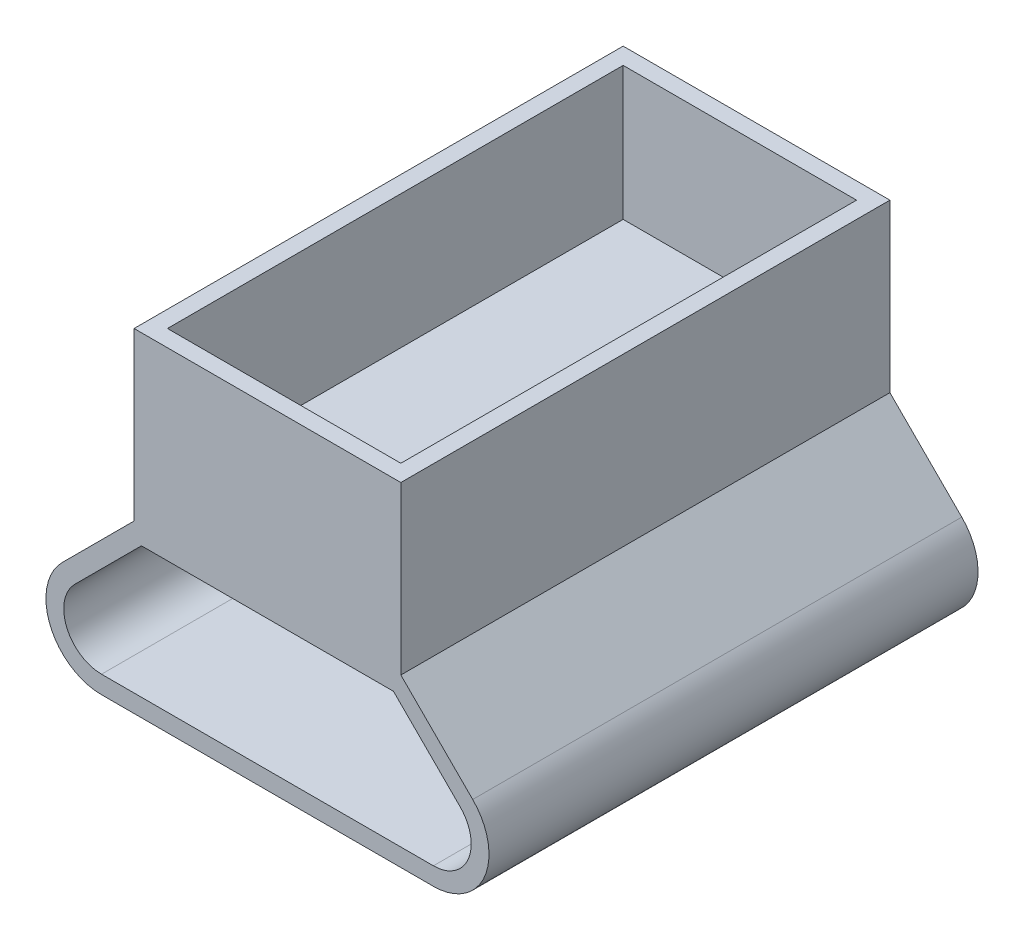
SolidWorks part; units mm, degrees
ref_plane "Front Plane" through (0, 0, 0) normal (0, 0, 1) x (1, 0, 0)
ref_plane "Top Plane" through (0, 0, 0) normal (0, 1, 0) x (1, 0, 0)
ref_plane "Right Plane" through (0, 0, 0) normal (1, 0, 0) x (0, 0, -1)
sketch "Sketch1" plane through (0, 0, 0) normal (0, 0, 1) x (1, 0, 0)
  line L0 (-12, 0) -> (12, 0)
  line L1 (-12, 0) -> (-18.4645, -6.4645)
  line L2 (-14.9289, -15) -> (14.9289, -15)
  line L3 (18.4645, -6.4645) -> (12, 0)
  arc A0 (-18.4645, -6.4645) -> (-14.9289, -15) centre (-14.9289, -10) ccw
  arc A1 (14.9289, -15) -> (18.4645, -6.4645) centre (14.9289, -10) ccw
  point P3 (-2.6993, 0)
  point P4 (0, 0)
  point P6 (0, 0)
  point P8 (-26.4535, -21.1639)
  point P9 (-33.5712, -21.6785)
  point P10 (-15.8198, 0)
  point P11 (-29.6264, -23.1363)
  point P12 (-16.9347, 0)
  point P13 (-16.3344, 0)
  point P14 (-16.4633, 0)
  point P15 (-33.2222, -17.6443)
  point P16 (-24.3682, -13.3682)
  point P17 (-26.5483, -15.5483)
  point P18 (-27.568, -16.568)
  dimension "D4" = 5
  dimension "D1" = 45
  dimension "D2" = 24
  dimension "D3" = 15
extrude "Boss-Extrude1" add sketch "Sketch1" along normal blind 44
sketch "Sketch3" plane through (0, 0, 44) normal (0, 0, 1) x (1, 0, 0)
  line L27 (-14.9289, -13.4) -> (14.9289, -13.4)
  line L28 (17.3331, -7.5958) -> (11.3373, -1.6)
  line L29 (11.3373, -1.6) -> (-11.3373, -1.6)
  line L30 (-11.3373, -1.6) -> (-17.3331, -7.5958)
  line L31 (-14.9289, -13.4) -> (14.9289, -13.4)
  line L32 (17.3331, -7.5958) -> (11.3373, -1.6)
  line L33 (11.3373, -1.6) -> (-11.3373, -1.6)
  line L34 (-11.3373, -1.6) -> (-17.3331, -7.5958)
  arc A6 (14.9289, -13.4) -> (17.3331, -7.5958) centre (14.9289, -10) ccw
  arc A7 (-17.3331, -7.5958) -> (-14.9289, -13.4) centre (-14.9289, -10) ccw
  arc A8 (14.9289, -13.4) -> (17.3331, -7.5958) centre (14.9289, -10) ccw
  arc A9 (-17.3331, -7.5958) -> (-14.9289, -13.4) centre (-14.9289, -10) ccw
  dimension "D1" = 1.6
extrude "Cut-Extrude1" cut sketch "Sketch3" against normal through all
sketch "Sketch2" plane through (0, 0, 0) normal (0, 1, 0) x (1, 0, 0)
  line L1 (-12, 0) -> (12, 0)
  line L2 (-12, 0) -> (-12, -44)
  line L3 (-12, -44) -> (12, -44)
  line L4 (12, 0) -> (12, -44)
  line L5 (-10.5, -1.5) -> (10.5, -1.5)
  line L6 (-10.5, -1.5) -> (-10.5, -42.5)
  line L7 (-10.5, -42.5) -> (10.5, -42.5)
  line L8 (10.5, -1.5) -> (10.5, -42.5)
  point P10 (-10.1511, -0.5328)
  point P11 (-10.4245, -0.4872)
  point P13 (0, -1.5)
  point P14 (-10.5, -22)
  point P15 (-12, -22)
  dimension "D1" = 41
  dimension "D2" = 21
extrude "Boss-Extrude2" add sketch "Sketch2" along normal blind 15
extrude "Boss-Extrude3" add sketch "Sketch2<2>" along normal blind 3 contours L8 L5 L6 L7 region at (0, 0, 22)
sketch "Sketch2<2>" plane through (0, 0, 0) normal (0, 1, 0) x (1, 0, 0) same geometry as "Sketch2"
